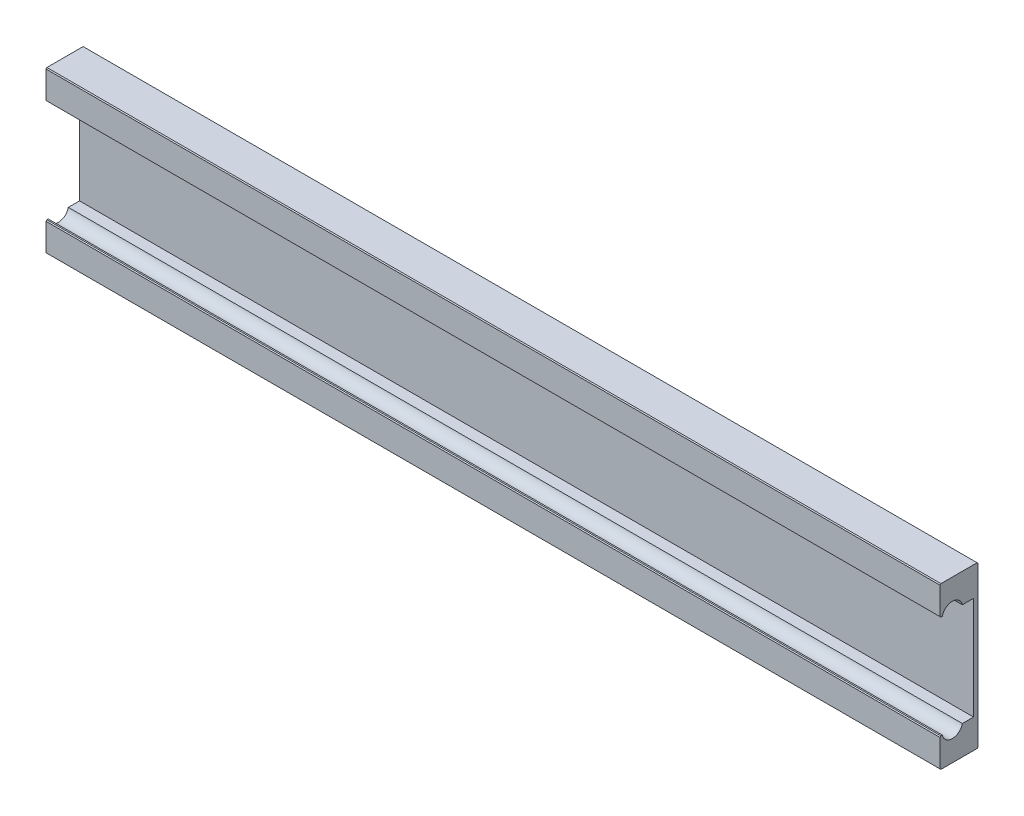
SolidWorks part; units mm, degrees
ref_plane "Front" through (0, 0, 0) normal (0, 0, 1) x (1, 0, 0)
ref_plane "Top" through (0, 0, 0) normal (0, 1, 0) x (1, 0, 0)
ref_plane "Right" through (0, 0, 0) normal (1, 0, 0) x (0, 0, -1)
sketch "Sketch1" plane through (0, 0, 0) normal (0, 0, 1) x (1, 0, 0)
  line L0 (-100, -4) -> (-100, 4) construction
  line L1 (100, -18) -> (-100, -18)
  line L2 (100, -18) -> (100, 18)
  line L3 (100, 18) -> (-100, 18)
  line L4 (-100, -18) -> (-100, 18)
  line L5 (100, -18) -> (-100, 18) construction
  line L6 (100, 18) -> (-100, -18) construction
  line L8 (100, 11) -> (-100, 11) construction
  point P0 (0, 0)
  dimension "D1" = 7
extrude "Boss-Extrude1" add sketch "Sketch1" against normal blind 1
sketch "Sketch2" plane through (0, 0, 0) normal (0, 0, 1) x (1, 0, 0)
  line L0 (-100, -18) -> (-100, 18) construction
  line L1 (100, 18) -> (-100, 18)
  line L2 (100, 18) -> (100, 11.5)
  line L3 (100, 11.5) -> (-100, 11.5)
  line L4 (-100, 18) -> (-100, 11.5)
  line L6 (100, -18) -> (-100, -18)
  line L7 (100, -18) -> (100, -11.5)
  line L8 (100, -11.5) -> (-100, -11.5)
  line L9 (-100, -18) -> (-100, -11.5)
  line L10 (-100, -18) -> (-100, 18) construction
  line L12 (100, 11) -> (-100, 11) construction
  dimension "D1" = 0.5
extrude "Boss-Extrude2" add sketch "Sketch2" along normal up to surface (7.5 mm away)
sketch "Sketch3" plane through (0, 0, 0) normal (1, 0, 0) x (0, 0, -1)
  circle A1 centre (-4.75, 11) radius 2.3
  circle A2 centre (-4.75, 11) radius 2.3
  dimension "D1" = 0
extrude "Top Slot" cut sketch "Sketch3" against normal through all both and the other way through all
mirror "Bottom Slot" about plane through (0, 0, 0) normal (0, 1, 0) of "Top Slot"
chamfer "Deburs" distance 0.2 angle 45 6 edges at (0, -11.5, 7.5) (0, -18, 7.5) (0, -18, -1) (0, 18, -1) (0, 11.5, 7.5) (0, 18, 7.5)
